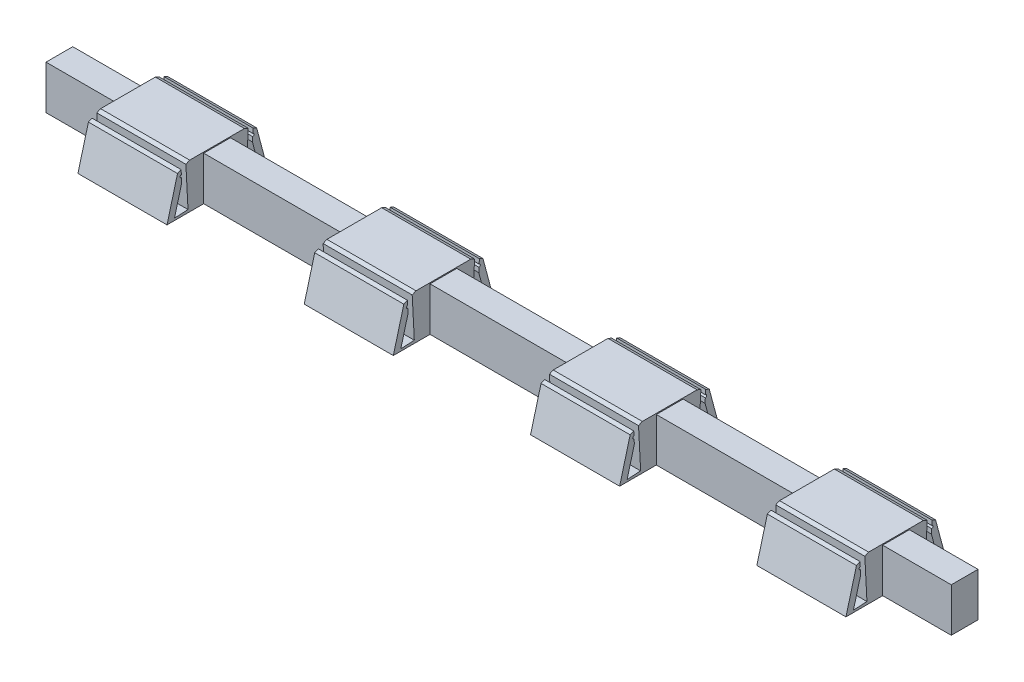
SolidWorks part; units mm, degrees
ref_plane "Front Plane" through (0, 0, 0) normal (0, 0, 1) x (1, 0, 0)
ref_plane "Top Plane" through (0, 0, 0) normal (0, 1, 0) x (1, 0, 0)
ref_plane "Right Plane" through (0, 0, 0) normal (1, 0, 0) x (0, 0, -1)
sketch "Sketch1" plane through (0, 0, 0) normal (1, 0, 0) x (0, 0, -1)
  line L0 (10.6865, 0.2453) -> (15.3672, 0) construction
  line L1 (10.4807, 5.1684) -> (10.8912, 5.1469) construction
  line L2 (12.2038, 9.1749) -> (12.0651, 6.528) construction
  line L3 (12.0651, 6.528) -> (13.6881, 0.4708)
  line L4 (13.6881, 0.4708) -> (10.6545, 0.6298)
  line L5 (10.6545, 0.6298) -> (11.128, 9.664)
  line L6 (11.128, 9.664) -> (10.2765, 10.051)
  line L7 (10.2765, 10.051) -> (10.6865, 0.2453) construction
  line L8 (12.2038, 9.1749) -> (12.1502, 8.151)
  line L9 (12.1188, 7.5518) -> (12.0651, 6.528)
  line L10 (12.2038, 9.1749) -> (13.0066, 8.81)
  line L11 (13.0066, 8.81) -> (15.3672, 0)
  line L12 (12.1713, 0.5503) -> (12.0002, 0.1765) construction
  line L13 (4.128, 0) -> (4.128, 7.6812) construction
  line L14 (-3.9154, 0.5503) -> (-3.7443, 0.1765) construction
  line L15 (-5.4322, 0.4708) -> (-2.3986, 0.6298)
  line L16 (-3.9479, 9.1749) -> (-3.8092, 6.528) construction
  line L17 (-2.2248, 5.1684) -> (-2.6353, 5.1469) construction
  line L18 (-2.4306, 0.2453) -> (-7.1113, 0) construction
  line L19 (-4.7506, 8.81) -> (-7.1113, 0)
  line L20 (-3.9479, 9.1749) -> (-4.7506, 8.81)
  line L21 (-3.8629, 7.5518) -> (-3.8092, 6.528)
  line L22 (-3.9479, 9.1749) -> (-3.8943, 8.151)
  line L23 (-2.0206, 10.051) -> (-2.4306, 0.2453) construction
  line L24 (-2.872, 9.664) -> (-2.0206, 10.051)
  line L25 (-2.3986, 0.6298) -> (-2.872, 9.664)
  line L26 (-3.8092, 6.528) -> (-5.4322, 0.4708)
  line L27 (-2.0206, 10.051) -> (10.2765, 10.051)
  line L28 (-7.1113, 0) -> (-2.3656, 0)
  line L29 (-2.3986, 0.6298) -> (-2.3656, 0)
  line L30 (10.6545, 0.6298) -> (10.6215, 0)
  line L31 (-2.3656, 0) -> (10.6215, 0)
  line L32 (10.6215, 0) -> (15.3672, 0)
  arc A0 (12.1502, 8.151) -> (12.1188, 7.5518) centre (12.1345, 7.8514) cw
  arc A1 (-3.8943, 8.151) -> (-3.8629, 7.5518) centre (-3.8786, 7.8514) ccw
  dimension "D1" = 0.3
  dimension "D2" = 1.1
  dimension "D3" = 72
  dimension "D4" = 1.5
  dimension "D5" = 14
extrude "Clip #1" add sketch "Sketch1" along normal mid plane 20 contours L28 L19 L20 L22 A1 L21 L26 L15 L25 L24 L27 L6 L5 L4 L3 L9 A0 L8 L10 L11 L32 L31
sketch "Sketch4" plane through (0, 0, 0) normal (1, 0, 0) x (0, 0, -1)
  line L0 (1.126, 9.8243) -> (1.126, 0)
  line L1 (-2.3656, 0) -> (10.6215, 0) construction
  line L2 (1.126, 9.8243) -> (7.13, 9.8243)
  line L3 (7.13, 9.8243) -> (7.13, 0)
  line L4 (7.13, 0) -> (1.126, 0)
  line L5 (4.128, -200000) -> (4.128, 200007.6812) construction
  point P5 (4.128, 9.8243)
  dimension "D1" = 6.004
extrude "Center beam" add sketch "Sketch4" along normal blind 177.8 and the other way blind 25.4
sketch "Sketch5" plane through (0, 0, 0) normal (0, 1, 0) x (1, 0, 0)
  line L0 (76.2, -58.3264) -> (76.2, 110.1277) construction
  line L1 (25.4, 19.5305) -> (25.4, 187.9846) construction
  line L2 (127, 16.9825) -> (127, 185.4366) construction
  line L3 (177.8, 22.3617) -> (177.8, 190.8158) construction
  dimension "D1" = 25.4
  dimension "D2" = 50.8
  dimension "D3" = 50.8
  dimension "D4" = 50.8
sketch3d "3DSketch2" plane through (0, 0, 0) normal (0, 0, 1) x (1, 0, 0)
  dimension "D1" = 25.4
sketch "Sketch6" plane through (25.4, 0, 0) normal (1, 0, 0) x (0, 0, -1)
  line L0 (13.6881, 0.4708) -> (10.6545, 0.6298) construction
  line L5 (12.0651, 6.528) -> (13.6881, 0.4708) construction
  line L6 (12.1188, 7.5518) -> (12.0651, 6.528) construction
  line L7 (12.2038, 9.1749) -> (12.1502, 8.151) construction
  line L8 (12.2038, 9.1749) -> (13.0066, 8.81) construction
  line L9 (13.0066, 8.81) -> (15.3672, 0) construction
  line L10 (10.6215, 0) -> (15.3672, 0) construction
  line L11 (10.6545, 0.6298) -> (11.128, 9.664) construction
  line L12 (11.128, 9.664) -> (10.2765, 10.051) construction
  line L13 (-2.0206, 10.051) -> (10.2765, 10.051) construction
  line L14 (-2.872, 9.664) -> (-2.0206, 10.051) construction
  line L15 (-2.3986, 0.6298) -> (-2.872, 9.664) construction
  line L16 (10.6545, 0.6298) -> (10.6215, 0) construction
  line L17 (-7.1113, 0) -> (-2.3656, 0) construction
  line L18 (-4.7506, 8.81) -> (-7.1113, 0) construction
  line L19 (-3.9479, 9.1749) -> (-4.7506, 8.81) construction
  line L20 (-3.9479, 9.1749) -> (-3.8943, 8.151) construction
  line L21 (-3.8629, 7.5518) -> (-3.8092, 6.528) construction
  line L22 (-3.8092, 6.528) -> (-5.4322, 0.4708) construction
  line L23 (-5.4322, 0.4708) -> (-2.3986, 0.6298) construction
  line L24 (-2.3986, 0.6298) -> (-2.3656, 0) construction
  line L25 (-2.3656, 0) -> (10.6215, 0) construction
  line L26 (13.6881, 0.4708) -> (10.6545, 0.6298)
  line L27 (12.0651, 6.528) -> (13.6881, 0.4708)
  line L28 (12.1188, 7.5518) -> (12.0651, 6.528)
  line L29 (12.2038, 9.1749) -> (12.1502, 8.151)
  line L30 (12.2038, 9.1749) -> (13.0066, 8.81)
  line L31 (13.0066, 8.81) -> (15.3672, 0)
  line L32 (10.6215, 0) -> (15.3672, 0)
  line L33 (10.6545, 0.6298) -> (11.128, 9.664)
  line L34 (11.128, 9.664) -> (10.2765, 10.051)
  line L35 (-2.0206, 10.051) -> (10.2765, 10.051)
  line L36 (-2.872, 9.664) -> (-2.0206, 10.051)
  line L37 (-2.3986, 0.6298) -> (-2.872, 9.664)
  line L38 (10.6545, 0.6298) -> (10.6215, 0) construction
  line L39 (-7.1113, 0) -> (-2.3656, 0)
  line L40 (-4.7506, 8.81) -> (-7.1113, 0)
  line L41 (-3.9479, 9.1749) -> (-4.7506, 8.81)
  line L42 (-3.9479, 9.1749) -> (-3.8943, 8.151)
  line L43 (-3.8629, 7.5518) -> (-3.8092, 6.528)
  line L44 (-3.8092, 6.528) -> (-5.4322, 0.4708)
  line L45 (-5.4322, 0.4708) -> (-2.3986, 0.6298)
  line L46 (-2.3986, 0.6298) -> (-2.3656, 0) construction
  line L47 (-2.3656, 0) -> (10.6215, 0)
  arc A0 (12.1188, 7.5518) -> (12.1502, 8.151) centre (12.1345, 7.8514) ccw construction
  arc A1 (-3.8943, 8.151) -> (-3.8629, 7.5518) centre (-3.8786, 7.8514) ccw construction
  arc A2 (12.1188, 7.5518) -> (12.1502, 8.151) centre (12.1345, 7.8514) ccw
  arc A3 (-3.8943, 8.151) -> (-3.8629, 7.5518) centre (-3.8786, 7.8514) ccw
extrude "Boss-Extrude9" [suppressed] add sketch "Sketch6" along normal mid plane 20 contours L37 L36 L35 L34 L33 L26 L27 L28 A2 L29 L30 L31 L32 L47 L39 L40 L41 L42 A3 L43 L44 L45
pattern_linear "LPattern1" count 4 spacing 50.8 along (1, 0, 0) of "Clip #1"
